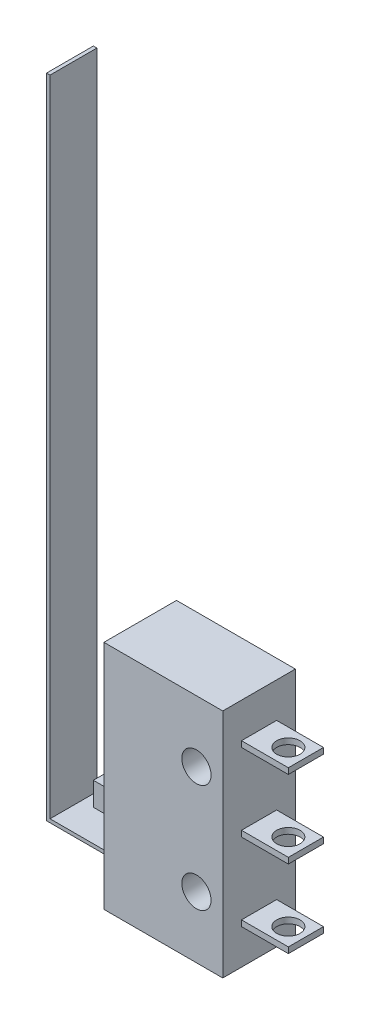
SolidWorks part; units mm, degrees
ref_plane "Front Plane" through (0, 0, 0) normal (0, 0, 1) x (1, 0, 0)
ref_plane "Top Plane" through (0, 0, 0) normal (0, 1, 0) x (1, 0, 0)
ref_plane "Right Plane" through (0, 0, 0) normal (1, 0, 0) x (0, 0, -1)
sketch "Sketch1" plane through (0, 0, 0) normal (0, 0, 1) x (1, 0, 0)
  line L1 (0, 0) -> (10.15, 0)
  line L2 (0, 0) -> (0, 19.75)
  line L3 (0, 19.75) -> (10.15, 19.75)
  line L4 (10.15, 0) -> (10.15, 19.75)
  dimension "D1" = 10.15
  dimension "D2" = 19.75
extrude "Boss-Extrude1" add sketch "Sketch1" against normal blind 6.2
sketch "Sketch2" plane through (0, 0, 0) normal (-1, 0, 0) x (0, 0, 1)
  line L0 (-6.2, 6) -> (0, 6) construction
  line L1 (-6.2, 19.75) -> (-6.2, 0) construction
  line L2 (0, 19.75) -> (0, 0) construction
  line L3 (-6.2, 0) -> (0, 0) construction
  line L4 (-3.1, 8) -> (-3.1, 6) construction
  line L5 (-5.1, 6) -> (-1.1, 6)
  line L6 (-5.1, 6) -> (-5.1, 8)
  line L7 (-5.1, 8) -> (-1.1, 8)
  line L8 (-1.1, 6) -> (-1.1, 8)
  line L9 (-3.1, 0) -> (-3.1, 2.9878) construction
  dimension "D1" = 6
  dimension "D2" = 4
  dimension "D4" = 2
extrude "Boss-Extrude2" add sketch "Sketch2" along normal blind 2
sketch "Sketch3" plane through (0, 0, 0) normal (-1, 0, 0) x (0, 0, 1)
  line L0 (-6.2, 3) -> (0, 3) construction
  line L1 (-6.2, 19.75) -> (-6.2, 0) construction
  line L2 (0, 19.75) -> (0, 0) construction
  line L3 (-6.2, 0) -> (0, 0) construction
  line L4 (-3.1, 0) -> (-3.1, 1.9674) construction
  line L5 (-5.1, 3) -> (-1.1, 3)
  line L6 (-5.1, 3) -> (-5.1, 3.3)
  line L7 (-5.1, 3.3) -> (-1.1, 3.3)
  line L8 (-1.1, 3) -> (-1.1, 3.3)
  line L9 (-3.1, 3.3) -> (-3.1, 3) construction
  dimension "D1" = 3
  dimension "D2" = 4
  dimension "D4" = 0.3
extrude "Boss-Extrude3" add sketch "Sketch3" along normal blind 6
sketch "Sketch4" plane through (0, 3.3, 0) normal (0, 1, 0) x (1, 0, 0)
  line L0 (-6, 1.1) -> (0, 1.1) construction
  line L1 (-6, 5.1) -> (-5.7, 5.1)
  line L2 (-6, 5.1) -> (-6, 1.1)
  line L3 (-6, 1.1) -> (-5.7, 1.1)
  line L4 (-5.7, 5.1) -> (-5.7, 1.1)
  dimension "D1" = 0.3
extrude "Boss-Extrude4" add sketch "Sketch4" along normal blind 55
sketch "Sketch5" plane through (10.15, 0, 0) normal (1, 0, 0) x (0, 0, -1)
  line L0 (3.1, 19.75) -> (3.1, 0) construction
  line L1 (6.2, 19.75) -> (0, 19.75) construction
  line L2 (6.2, 0) -> (0, 0) construction
  line L4 (1.6, 3.5) -> (4.6, 3.5)
  line L5 (1.6, 3.5) -> (1.6, 3)
  line L6 (1.6, 3) -> (4.6, 3)
  line L7 (4.6, 3.5) -> (4.6, 3)
  line L8 (1.6, 3.5) -> (4.6, 3) construction
  line L9 (1.6, 3) -> (4.6, 3.5) construction
  line L10 (1.6, 10.125) -> (4.6, 10.125)
  line L11 (1.6, 10.125) -> (1.6, 9.625)
  line L12 (1.6, 9.625) -> (4.6, 9.625)
  line L13 (4.6, 10.125) -> (4.6, 9.625)
  line L14 (1.6, 10.125) -> (4.6, 9.625) construction
  line L15 (1.6, 9.625) -> (4.6, 10.125) construction
  line L16 (1.6, 16.75) -> (4.6, 16.75)
  line L17 (1.6, 16.75) -> (1.6, 16.25)
  line L18 (1.6, 16.25) -> (4.6, 16.25)
  line L19 (4.6, 16.75) -> (4.6, 16.25)
  line L20 (1.6, 16.75) -> (4.6, 16.25) construction
  line L21 (1.6, 16.25) -> (4.6, 16.75) construction
  point P6 (3.1, 3.25)
  point P11 (3.1, 9.875)
  point P16 (3.1, 16.5)
  point P21 (3.1, 9.875)
  point P22 (3.1, 3.25)
  dimension "D1" = 0.5
  dimension "D2" = 0.5
  dimension "D3" = 0.5
  dimension "D4" = 3
  dimension "D5" = 3
  dimension "D6" = 3
  dimension "D7" = 3
  dimension "D8" = 3
extrude "Boss-Extrude5" add sketch "Sketch5" along normal blind 4
sketch "Sketch6" plane through (0, 16.75, 0) normal (0, 1, 0) x (1, 0, 0)
  line L0 (14.15, 3.1) -> (10.15, 3.1) construction
  line L1 (14.15, 4.6) -> (14.15, 1.6) construction
  line L2 (10.15, 4.6) -> (10.15, 1.6) construction
  circle A0 centre (12.65, 3.1) radius 1
  point P8 (12.7838, 3.1)
  dimension "D1" = 2
  dimension "D2" = 1.5
extrude "Cut-Extrude1" cut sketch "Sketch6" against normal through all
sketch "Sketch7" plane through (0, 0, 0) normal (0, 0, 1) x (1, 0, 0)
  line L0 (10.15, 0) -> (10.15, 19.75) construction
  line L1 (0, 0) -> (10.15, 0) construction
  line L2 (10.15, 19.75) -> (0, 19.75) construction
  circle A0 centre (7.9, 5.25) radius 1.25
  circle A1 centre (7.9, 14.5) radius 1.25
  dimension "D1" = 2.5
  dimension "D2" = 2.5
  dimension "D3" = 2.25
  dimension "D4" = 2.25
  dimension "D5" = 5.25
  dimension "D6" = 5.25
extrude "Cut-Extrude2" cut sketch "Sketch7" against normal through all
